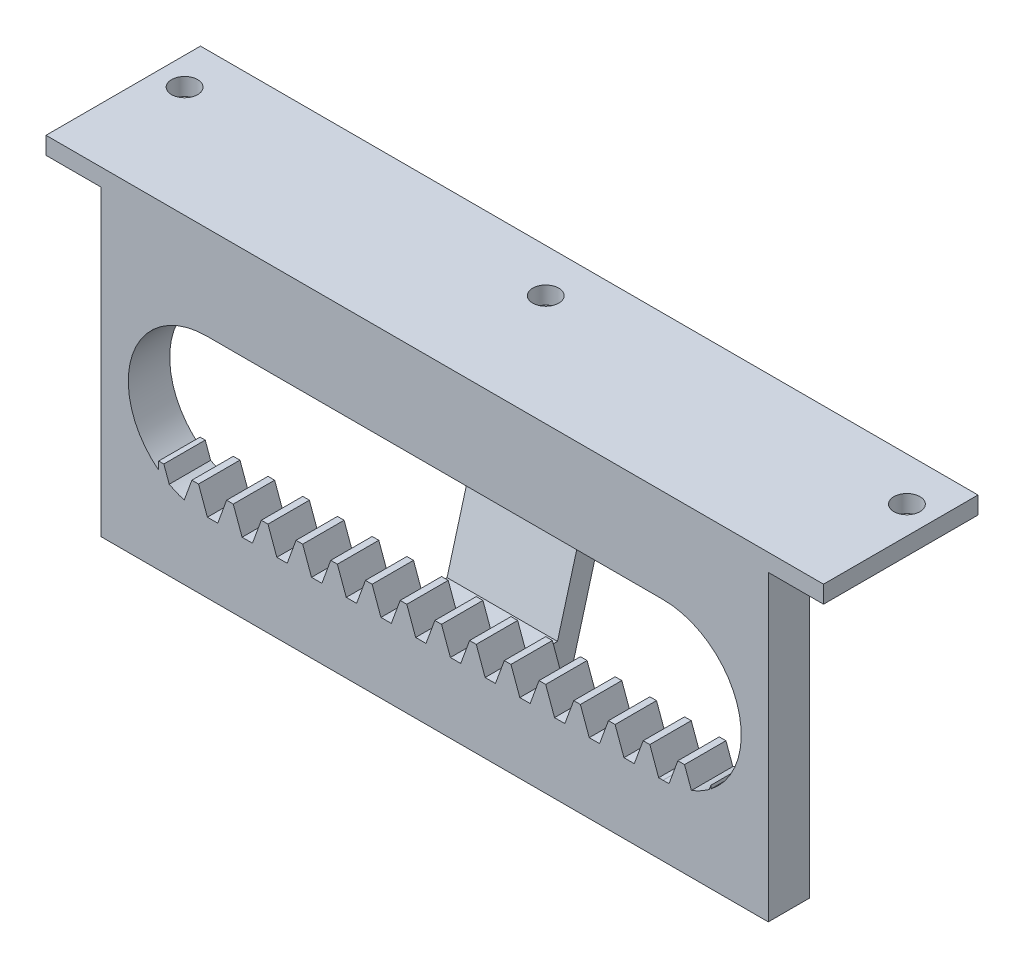
SolidWorks part; units mm, degrees
material "Nylon 101"
ref_plane "Front Plane" through (0, 0, 0) normal (0, 0, 1) x (1, 0, 0)
ref_plane "Top Plane" through (0, 0, 0) normal (0, 1, 0) x (1, 0, 0)
ref_plane "Right Plane" through (0, 0, 0) normal (1, 0, 0) x (0, 0, -1)
sketch "Sketch1" plane through (0, 0, 0) normal (0, 1, 0) x (1, 0, 0)
  line L0 (0, 0) -> (0, 4.7625)
  line L1 (0, 4.7625) -> (63.5, 4.7625)
  line L2 (63.5, 4.7625) -> (63.5, 0)
  line L3 (63.5, 0) -> (0, 0)
  dimension "D1" = 4.7625
  dimension "D2" = 63.5
extrude "Boss-Extrude1" add sketch "Sketch1" along normal blind 4.5
sketch "Sketch2" plane through (0, 0, 0) normal (0, 0, 1) x (1, 0, 0)
  line L0 (0, 3.2275) -> (63.5, 3.2275) construction
  line L1 (0, 4.5) -> (0, 0) construction
  line L2 (63.5, 4.5) -> (63.5, 0) construction
  line L3 (0, 1.7035) -> (63.5, 1.7035) construction
  line L4 (0, 4.5) -> (63.5, 4.5) construction
  line L5 (0, 4.5) -> (0.5952, 4.5) construction
  line L6 (0.5952, 4.5) -> (1.613, 1.7035)
  line L7 (1.613, 1.7035) -> (2.2082, 1.7035)
  line L8 (2.8034, 1.7035) -> (3.8212, 4.5)
  line L9 (3.8212, 4.5) -> (4.4164, 4.5) construction
  line L10 (2.2082, 1.7035) -> (2.8034, 1.7035)
  line L11 (0.5952, 4.5) -> (3.8212, 4.5)
  line L12 (4.5868, 4.5) -> (5.6047, 1.7035)
  line L13 (5.6047, 1.7035) -> (6.1999, 1.7035)
  line L14 (6.795, 1.7035) -> (7.8129, 4.5)
  line L15 (6.1999, 1.7035) -> (6.795, 1.7035)
  line L16 (4.5868, 4.5) -> (7.8129, 4.5)
  line L17 (3.9917, 4.5) -> (4.5868, 4.5) construction
  line L18 (7.8129, 4.5) -> (8.4081, 4.5) construction
  line L19 (8.5785, 4.5) -> (9.5964, 1.7035)
  line L20 (9.5964, 1.7035) -> (10.1915, 1.7035)
  line L21 (10.7867, 1.7035) -> (11.8046, 4.5)
  line L22 (10.1915, 1.7035) -> (10.7867, 1.7035)
  line L23 (8.5785, 4.5) -> (11.8046, 4.5)
  line L24 (7.9834, 4.5) -> (8.5785, 4.5) construction
  line L25 (11.8046, 4.5) -> (12.3997, 4.5) construction
  line L26 (12.5702, 4.5) -> (13.5881, 1.7035)
  line L27 (13.5881, 1.7035) -> (14.1832, 1.7035)
  line L28 (14.7784, 1.7035) -> (15.7962, 4.5)
  line L29 (14.1832, 1.7035) -> (14.7784, 1.7035)
  line L30 (12.5702, 4.5) -> (15.7962, 4.5)
  line L31 (11.975, 4.5) -> (12.5702, 4.5) construction
  line L32 (15.7962, 4.5) -> (16.3914, 4.5) construction
  line L33 (16.5619, 4.5) -> (17.5797, 1.7035)
  line L34 (17.5797, 1.7035) -> (18.1749, 1.7035)
  line L35 (18.7701, 1.7035) -> (19.7879, 4.5)
  line L36 (18.1749, 1.7035) -> (18.7701, 1.7035)
  line L37 (16.5619, 4.5) -> (19.7879, 4.5)
  line L38 (15.9667, 4.5) -> (16.5619, 4.5) construction
  line L39 (19.7879, 4.5) -> (20.3831, 4.5) construction
  line L40 (20.5535, 4.5) -> (21.5714, 1.7035)
  line L41 (21.5714, 1.7035) -> (22.1666, 1.7035)
  line L42 (22.7617, 1.7035) -> (23.7796, 4.5)
  line L43 (22.1666, 1.7035) -> (22.7617, 1.7035)
  line L44 (20.5535, 4.5) -> (23.7796, 4.5)
  line L45 (19.9584, 4.5) -> (20.5535, 4.5) construction
  line L46 (23.7796, 4.5) -> (24.3748, 4.5) construction
  line L47 (24.5452, 4.5) -> (25.5631, 1.7035)
  line L48 (25.5631, 1.7035) -> (26.1582, 1.7035)
  line L49 (26.7534, 1.7035) -> (27.7713, 4.5)
  line L50 (26.1582, 1.7035) -> (26.7534, 1.7035)
  line L51 (24.5452, 4.5) -> (27.7713, 4.5)
  line L52 (23.9501, 4.5) -> (24.5452, 4.5) construction
  line L53 (27.7713, 4.5) -> (28.3664, 4.5) construction
  line L54 (28.5369, 4.5) -> (29.5548, 1.7035)
  line L55 (29.5548, 1.7035) -> (30.1499, 1.7035)
  line L56 (30.7451, 1.7035) -> (31.763, 4.5)
  line L57 (30.1499, 1.7035) -> (30.7451, 1.7035)
  line L58 (28.5369, 4.5) -> (31.763, 4.5)
  line L59 (27.9417, 4.5) -> (28.5369, 4.5) construction
  line L60 (31.763, 4.5) -> (32.3581, 4.5) construction
  line L61 (32.5286, 4.5) -> (33.5464, 1.7035)
  line L62 (33.5464, 1.7035) -> (34.1416, 1.7035)
  line L63 (34.7368, 1.7035) -> (35.7546, 4.5)
  line L64 (34.1416, 1.7035) -> (34.7368, 1.7035)
  line L65 (32.5286, 4.5) -> (35.7546, 4.5)
  line L66 (31.9334, 4.5) -> (32.5286, 4.5) construction
  line L67 (35.7546, 4.5) -> (36.3498, 4.5) construction
  line L68 (36.5203, 4.5) -> (37.5381, 1.7035)
  line L69 (37.5381, 1.7035) -> (38.1333, 1.7035)
  line L70 (38.7284, 1.7035) -> (39.7463, 4.5)
  line L71 (38.1333, 1.7035) -> (38.7284, 1.7035)
  line L72 (36.5203, 4.5) -> (39.7463, 4.5)
  line L73 (35.9251, 4.5) -> (36.5203, 4.5) construction
  line L74 (39.7463, 4.5) -> (40.3415, 4.5) construction
  line L75 (40.5119, 4.5) -> (41.5298, 1.7035)
  line L76 (41.5298, 1.7035) -> (42.125, 1.7035)
  line L77 (42.7201, 1.7035) -> (43.738, 4.5)
  line L78 (42.125, 1.7035) -> (42.7201, 1.7035)
  line L79 (40.5119, 4.5) -> (43.738, 4.5)
  line L80 (39.9168, 4.5) -> (40.5119, 4.5) construction
  line L81 (43.738, 4.5) -> (44.3331, 4.5) construction
  line L82 (44.5036, 4.5) -> (45.5215, 1.7035)
  line L83 (45.5215, 1.7035) -> (46.1166, 1.7035)
  line L84 (46.7118, 1.7035) -> (47.7297, 4.5)
  line L85 (46.1166, 1.7035) -> (46.7118, 1.7035)
  line L86 (44.5036, 4.5) -> (47.7297, 4.5)
  line L87 (43.9084, 4.5) -> (44.5036, 4.5) construction
  line L88 (47.7297, 4.5) -> (48.3248, 4.5) construction
  line L89 (48.4953, 4.5) -> (49.5131, 1.7035)
  line L90 (49.5131, 1.7035) -> (50.1083, 1.7035)
  line L91 (50.7035, 1.7035) -> (51.7213, 4.5)
  line L92 (50.1083, 1.7035) -> (50.7035, 1.7035)
  line L93 (48.4953, 4.5) -> (51.7213, 4.5)
  line L94 (47.9001, 4.5) -> (48.4953, 4.5) construction
  line L95 (51.7213, 4.5) -> (52.3165, 4.5) construction
  line L96 (52.487, 4.5) -> (53.5048, 1.7035)
  line L97 (53.5048, 1.7035) -> (54.1, 1.7035)
  line L98 (54.6952, 1.7035) -> (55.713, 4.5)
  line L99 (54.1, 1.7035) -> (54.6952, 1.7035)
  line L100 (52.487, 4.5) -> (55.713, 4.5)
  line L101 (51.8918, 4.5) -> (52.487, 4.5) construction
  line L102 (55.713, 4.5) -> (56.3082, 4.5) construction
  line L103 (56.4786, 4.5) -> (57.4965, 1.7035)
  line L104 (57.4965, 1.7035) -> (58.0917, 1.7035)
  line L105 (58.6868, 1.7035) -> (59.7047, 4.5)
  line L106 (58.0917, 1.7035) -> (58.6868, 1.7035)
  line L107 (56.4786, 4.5) -> (59.7047, 4.5)
  line L108 (55.8835, 4.5) -> (56.4786, 4.5) construction
  line L109 (59.7047, 4.5) -> (60.2999, 4.5) construction
  line L110 (60.4703, 4.5) -> (61.4882, 1.7035)
  line L111 (61.4882, 1.7035) -> (62.0833, 1.7035)
  line L112 (62.6785, 1.7035) -> (63.6964, 4.5)
  line L113 (62.0833, 1.7035) -> (62.6785, 1.7035)
  line L114 (60.4703, 4.5) -> (63.6964, 4.5)
  line L115 (59.8751, 4.5) -> (60.4703, 4.5) construction
  line L116 (63.6964, 4.5) -> (64.2915, 4.5) construction
  line L117 (64.462, 4.5) -> (65.4798, 1.7035)
  line L118 (65.4798, 1.7035) -> (66.075, 1.7035)
  line L119 (66.6702, 1.7035) -> (67.688, 4.5)
  line L120 (66.075, 1.7035) -> (66.6702, 1.7035)
  line L121 (64.462, 4.5) -> (67.688, 4.5)
  line L122 (63.8668, 4.5) -> (64.462, 4.5) construction
  line L123 (67.688, 4.5) -> (68.2832, 4.5) construction
  line L124 (68.4537, 4.5) -> (69.4715, 1.7035)
  line L125 (69.4715, 1.7035) -> (70.0667, 1.7035)
  line L126 (70.6619, 1.7035) -> (71.6797, 4.5)
  line L127 (70.0667, 1.7035) -> (70.6619, 1.7035)
  line L128 (68.4537, 4.5) -> (71.6797, 4.5)
  line L129 (67.8585, 4.5) -> (68.4537, 4.5) construction
  line L130 (71.6797, 4.5) -> (72.2749, 4.5) construction
  line L131 (72.4453, 4.5) -> (73.4632, 1.7035)
  line L132 (73.4632, 1.7035) -> (74.0584, 1.7035)
  line L133 (74.6535, 1.7035) -> (75.6714, 4.5)
  line L134 (74.0584, 1.7035) -> (74.6535, 1.7035)
  line L135 (72.4453, 4.5) -> (75.6714, 4.5)
  line L136 (71.8502, 4.5) -> (72.4453, 4.5) construction
  line L137 (75.6714, 4.5) -> (76.2666, 4.5) construction
  line L138 (76.437, 4.5) -> (77.4549, 1.7035)
  line L139 (77.4549, 1.7035) -> (78.05, 1.7035)
  line L140 (78.6452, 1.7035) -> (79.6631, 4.5)
  line L141 (78.05, 1.7035) -> (78.6452, 1.7035)
  line L142 (76.437, 4.5) -> (79.6631, 4.5)
  line L143 (75.8418, 4.5) -> (76.437, 4.5) construction
  line L144 (79.6631, 4.5) -> (80.2582, 4.5) construction
  line L145 (80.4287, 4.5) -> (81.4465, 1.7035)
  line L146 (81.4465, 1.7035) -> (82.0417, 1.7035)
  line L147 (82.6369, 1.7035) -> (83.6547, 4.5)
  line L148 (82.0417, 1.7035) -> (82.6369, 1.7035)
  line L149 (80.4287, 4.5) -> (83.6547, 4.5)
  line L150 (79.8335, 4.5) -> (80.4287, 4.5) construction
  line L151 (83.6547, 4.5) -> (84.2499, 4.5) construction
  line L152 (84.4204, 4.5) -> (85.4382, 1.7035)
  line L153 (85.4382, 1.7035) -> (86.0334, 1.7035)
  line L154 (86.6286, 1.7035) -> (87.6464, 4.5)
  line L155 (86.0334, 1.7035) -> (86.6286, 1.7035)
  line L156 (84.4204, 4.5) -> (87.6464, 4.5)
  line L157 (83.8252, 4.5) -> (84.4204, 4.5) construction
  line L158 (87.6464, 4.5) -> (88.2416, 4.5) construction
  line L159 (88.412, 4.5) -> (89.4299, 1.7035)
  line L160 (89.4299, 1.7035) -> (90.0251, 1.7035)
  line L161 (90.6202, 1.7035) -> (91.6381, 4.5)
  line L162 (90.0251, 1.7035) -> (90.6202, 1.7035)
  line L163 (88.412, 4.5) -> (91.6381, 4.5)
  line L164 (87.8169, 4.5) -> (88.412, 4.5) construction
  line L165 (91.6381, 4.5) -> (92.2333, 4.5) construction
  line L166 (92.4037, 4.5) -> (93.4216, 1.7035)
  line L167 (93.4216, 1.7035) -> (94.0167, 1.7035)
  line L168 (94.6119, 1.7035) -> (95.6298, 4.5)
  line L169 (94.0167, 1.7035) -> (94.6119, 1.7035)
  line L170 (92.4037, 4.5) -> (95.6298, 4.5)
  line L171 (91.8086, 4.5) -> (92.4037, 4.5) construction
  line L172 (95.6298, 4.5) -> (96.2249, 4.5) construction
  line L173 (96.3954, 4.5) -> (97.4133, 1.7035)
  line L174 (97.4133, 1.7035) -> (98.0084, 1.7035)
  line L175 (98.6036, 1.7035) -> (99.6214, 4.5)
  line L176 (98.0084, 1.7035) -> (98.6036, 1.7035)
  line L177 (96.3954, 4.5) -> (99.6214, 4.5)
  line L178 (95.8002, 4.5) -> (96.3954, 4.5) construction
  line L179 (99.6214, 4.5) -> (100.2166, 4.5) construction
  line L180 (100.3871, 4.5) -> (101.4049, 1.7035)
  line L181 (101.4049, 1.7035) -> (102.0001, 1.7035)
  line L182 (102.5953, 1.7035) -> (103.6131, 4.5)
  line L183 (102.0001, 1.7035) -> (102.5953, 1.7035)
  line L184 (100.3871, 4.5) -> (103.6131, 4.5)
  line L185 (99.7919, 4.5) -> (100.3871, 4.5) construction
  line L186 (103.6131, 4.5) -> (104.2083, 4.5) construction
  line L187 (104.3787, 4.5) -> (105.3966, 1.7035)
  line L188 (105.3966, 1.7035) -> (105.9918, 1.7035)
  line L189 (106.5869, 1.7035) -> (107.6048, 4.5)
  line L190 (105.9918, 1.7035) -> (106.5869, 1.7035)
  line L191 (104.3787, 4.5) -> (107.6048, 4.5)
  line L192 (103.7836, 4.5) -> (104.3787, 4.5) construction
  line L193 (107.6048, 4.5) -> (108.2, 4.5) construction
  line L194 (108.3704, 4.5) -> (109.3883, 1.7035)
  line L195 (109.3883, 1.7035) -> (109.9835, 1.7035)
  line L196 (110.5786, 1.7035) -> (111.5965, 4.5)
  line L197 (109.9835, 1.7035) -> (110.5786, 1.7035)
  line L198 (108.3704, 4.5) -> (111.5965, 4.5)
  line L199 (107.7753, 4.5) -> (108.3704, 4.5) construction
  line L200 (111.5965, 4.5) -> (112.1916, 4.5) construction
  line L201 (112.3621, 4.5) -> (113.38, 1.7035)
  line L202 (113.38, 1.7035) -> (113.9751, 1.7035)
  line L203 (114.5703, 1.7035) -> (115.5882, 4.5)
  line L204 (113.9751, 1.7035) -> (114.5703, 1.7035)
  line L205 (112.3621, 4.5) -> (115.5882, 4.5)
  line L206 (111.7669, 4.5) -> (112.3621, 4.5) construction
  line L207 (115.5882, 4.5) -> (116.1833, 4.5) construction
  line L208 (116.3538, 4.5) -> (117.3716, 1.7035)
  line L209 (117.3716, 1.7035) -> (117.9668, 1.7035)
  line L210 (118.562, 1.7035) -> (119.5798, 4.5)
  line L211 (117.9668, 1.7035) -> (118.562, 1.7035)
  line L212 (116.3538, 4.5) -> (119.5798, 4.5)
  line L213 (115.7586, 4.5) -> (116.3538, 4.5) construction
  line L214 (119.5798, 4.5) -> (120.175, 4.5) construction
  line L215 (120.3455, 4.5) -> (121.3633, 1.7035)
  line L216 (121.3633, 1.7035) -> (121.9585, 1.7035)
  line L217 (122.5536, 1.7035) -> (123.5715, 4.5)
  line L218 (121.9585, 1.7035) -> (122.5536, 1.7035)
  line L219 (120.3455, 4.5) -> (123.5715, 4.5)
  line L220 (119.7503, 4.5) -> (120.3455, 4.5) construction
  line L221 (123.5715, 4.5) -> (124.1667, 4.5) construction
  line L222 (124.3371, 4.5) -> (125.355, 1.7035)
  line L223 (125.355, 1.7035) -> (125.9502, 1.7035)
  line L224 (126.5453, 1.7035) -> (127.5632, 4.5)
  line L225 (125.9502, 1.7035) -> (126.5453, 1.7035)
  line L226 (124.3371, 4.5) -> (127.5632, 4.5)
  line L227 (123.742, 4.5) -> (124.3371, 4.5) construction
  line L228 (127.5632, 4.5) -> (128.1583, 4.5) construction
  line L229 (128.3288, 4.5) -> (129.3467, 1.7035)
  line L230 (129.3467, 1.7035) -> (129.9418, 1.7035)
  line L231 (130.537, 1.7035) -> (131.5549, 4.5)
  line L232 (129.9418, 1.7035) -> (130.537, 1.7035)
  line L233 (128.3288, 4.5) -> (131.5549, 4.5)
  line L234 (127.7336, 4.5) -> (128.3288, 4.5) construction
  line L235 (131.5549, 4.5) -> (132.15, 4.5) construction
  line L236 (132.3205, 4.5) -> (133.3383, 1.7035)
  line L237 (133.3383, 1.7035) -> (133.9335, 1.7035)
  line L238 (134.5287, 1.7035) -> (135.5465, 4.5)
  line L239 (133.9335, 1.7035) -> (134.5287, 1.7035)
  line L240 (132.3205, 4.5) -> (135.5465, 4.5)
  line L241 (131.7253, 4.5) -> (132.3205, 4.5) construction
  line L242 (135.5465, 4.5) -> (136.1417, 4.5) construction
  line L243 (136.3122, 4.5) -> (137.33, 1.7035)
  line L244 (137.33, 1.7035) -> (137.9252, 1.7035)
  line L245 (138.5204, 1.7035) -> (139.5382, 4.5)
  line L246 (137.9252, 1.7035) -> (138.5204, 1.7035)
  line L247 (136.3122, 4.5) -> (139.5382, 4.5)
  line L248 (135.717, 4.5) -> (136.3122, 4.5) construction
  line L249 (139.5382, 4.5) -> (140.1334, 4.5) construction
  line L250 (140.3038, 4.5) -> (141.3217, 1.7035)
  line L251 (141.3217, 1.7035) -> (141.9169, 1.7035)
  line L252 (142.512, 1.7035) -> (143.5299, 4.5)
  line L253 (141.9169, 1.7035) -> (142.512, 1.7035)
  line L254 (140.3038, 4.5) -> (143.5299, 4.5)
  line L255 (139.7087, 4.5) -> (140.3038, 4.5) construction
  line L256 (143.5299, 4.5) -> (144.1251, 4.5) construction
  line L257 (144.2955, 4.5) -> (145.3134, 1.7035)
  line L258 (145.3134, 1.7035) -> (145.9085, 1.7035)
  line L259 (146.5037, 1.7035) -> (147.5216, 4.5)
  line L260 (145.9085, 1.7035) -> (146.5037, 1.7035)
  line L261 (144.2955, 4.5) -> (147.5216, 4.5)
  line L262 (143.7003, 4.5) -> (144.2955, 4.5) construction
  line L263 (147.5216, 4.5) -> (148.1167, 4.5) construction
  line L264 (148.2872, 4.5) -> (149.305, 1.7035)
  line L265 (149.305, 1.7035) -> (149.9002, 1.7035)
  line L266 (150.4954, 1.7035) -> (151.5132, 4.5)
  line L267 (149.9002, 1.7035) -> (150.4954, 1.7035)
  line L268 (148.2872, 4.5) -> (151.5132, 4.5)
  line L269 (147.692, 4.5) -> (148.2872, 4.5) construction
  line L270 (151.5132, 4.5) -> (152.1084, 4.5) construction
  line L271 (152.2789, 4.5) -> (153.2967, 1.7035)
  line L272 (153.2967, 1.7035) -> (153.8919, 1.7035)
  line L273 (154.4871, 1.7035) -> (155.5049, 4.5)
  line L274 (153.8919, 1.7035) -> (154.4871, 1.7035)
  line L275 (152.2789, 4.5) -> (155.5049, 4.5)
  line L276 (151.6837, 4.5) -> (152.2789, 4.5) construction
  line L277 (155.5049, 4.5) -> (156.1001, 4.5) construction
  line L278 (156.2705, 4.5) -> (157.2884, 1.7035)
  line L279 (157.2884, 1.7035) -> (157.8836, 1.7035)
  line L280 (158.4787, 1.7035) -> (159.4966, 4.5)
  line L281 (157.8836, 1.7035) -> (158.4787, 1.7035)
  line L282 (156.2705, 4.5) -> (159.4966, 4.5)
  line L283 (155.6754, 4.5) -> (156.2705, 4.5) construction
  line L284 (159.4966, 4.5) -> (160.0918, 4.5) construction
  line L285 (160.2622, 4.5) -> (161.2801, 1.7035)
  line L286 (161.2801, 1.7035) -> (161.8752, 1.7035)
  line L287 (162.4704, 1.7035) -> (163.4883, 4.5)
  line L288 (161.8752, 1.7035) -> (162.4704, 1.7035)
  line L289 (160.2622, 4.5) -> (163.4883, 4.5)
  line L290 (159.667, 4.5) -> (160.2622, 4.5) construction
  line L291 (163.4883, 4.5) -> (164.0834, 4.5) construction
  line L292 (164.2539, 4.5) -> (165.2718, 1.7035)
  line L293 (165.2718, 1.7035) -> (165.8669, 1.7035)
  line L294 (166.4621, 1.7035) -> (167.4799, 4.5)
  line L295 (165.8669, 1.7035) -> (166.4621, 1.7035)
  line L296 (164.2539, 4.5) -> (167.4799, 4.5)
  line L297 (163.6587, 4.5) -> (164.2539, 4.5) construction
  line L298 (167.4799, 4.5) -> (168.0751, 4.5) construction
  line L299 (168.2456, 4.5) -> (169.2634, 1.7035)
  line L300 (169.2634, 1.7035) -> (169.8586, 1.7035)
  line L301 (170.4538, 1.7035) -> (171.4716, 4.5)
  line L302 (169.8586, 1.7035) -> (170.4538, 1.7035)
  line L303 (168.2456, 4.5) -> (171.4716, 4.5)
  line L304 (167.6504, 4.5) -> (168.2456, 4.5) construction
  line L305 (171.4716, 4.5) -> (172.0668, 4.5) construction
  line L306 (172.2372, 4.5) -> (173.2551, 1.7035)
  line L307 (173.2551, 1.7035) -> (173.8503, 1.7035)
  line L308 (174.4454, 1.7035) -> (175.4633, 4.5)
  line L309 (173.8503, 1.7035) -> (174.4454, 1.7035)
  line L310 (172.2372, 4.5) -> (175.4633, 4.5)
  line L311 (171.6421, 4.5) -> (172.2372, 4.5) construction
  line L312 (175.4633, 4.5) -> (176.0585, 4.5) construction
  line L313 (176.2289, 4.5) -> (177.2468, 1.7035)
  line L314 (177.2468, 1.7035) -> (177.8419, 1.7035)
  line L315 (178.4371, 1.7035) -> (179.455, 4.5)
  line L316 (177.8419, 1.7035) -> (178.4371, 1.7035)
  line L317 (176.2289, 4.5) -> (179.455, 4.5)
  line L318 (175.6338, 4.5) -> (176.2289, 4.5) construction
  line L319 (179.455, 4.5) -> (180.0501, 4.5) construction
  line L320 (180.2206, 4.5) -> (181.2385, 1.7035)
  line L321 (181.2385, 1.7035) -> (181.8336, 1.7035)
  line L322 (182.4288, 1.7035) -> (183.4466, 4.5)
  line L323 (181.8336, 1.7035) -> (182.4288, 1.7035)
  line L324 (180.2206, 4.5) -> (183.4466, 4.5)
  line L325 (179.6254, 4.5) -> (180.2206, 4.5) construction
  line L326 (183.4466, 4.5) -> (184.0418, 4.5) construction
  line L327 (184.2123, 4.5) -> (185.2301, 1.7035)
  line L328 (185.2301, 1.7035) -> (185.8253, 1.7035)
  line L329 (186.4205, 1.7035) -> (187.4383, 4.5)
  line L330 (185.8253, 1.7035) -> (186.4205, 1.7035)
  line L331 (184.2123, 4.5) -> (187.4383, 4.5)
  line L332 (183.6171, 4.5) -> (184.2123, 4.5) construction
  line L333 (187.4383, 4.5) -> (188.0335, 4.5) construction
  line L334 (188.204, 4.5) -> (189.2218, 1.7035)
  line L335 (189.2218, 1.7035) -> (189.817, 1.7035)
  line L336 (190.4121, 1.7035) -> (191.43, 4.5)
  line L337 (189.817, 1.7035) -> (190.4121, 1.7035)
  line L338 (188.204, 4.5) -> (191.43, 4.5)
  line L339 (187.6088, 4.5) -> (188.204, 4.5) construction
  line L340 (191.43, 4.5) -> (192.0252, 4.5) construction
  line L341 (192.1956, 4.5) -> (193.2135, 1.7035)
  line L342 (193.2135, 1.7035) -> (193.8087, 1.7035)
  line L343 (194.4038, 1.7035) -> (195.4217, 4.5)
  line L344 (193.8087, 1.7035) -> (194.4038, 1.7035)
  line L345 (192.1956, 4.5) -> (195.4217, 4.5)
  line L346 (191.6005, 4.5) -> (192.1956, 4.5) construction
  line L347 (195.4217, 4.5) -> (196.0168, 4.5) construction
  line L348 (196.1873, 4.5) -> (197.2052, 1.7035)
  line L349 (197.2052, 1.7035) -> (197.8003, 1.7035)
  line L350 (198.3955, 1.7035) -> (199.4134, 4.5)
  line L351 (197.8003, 1.7035) -> (198.3955, 1.7035)
  line L352 (196.1873, 4.5) -> (199.4134, 4.5)
  line L353 (195.5921, 4.5) -> (196.1873, 4.5) construction
  line L354 (199.4134, 4.5) -> (200.0085, 4.5) construction
  line L355 (200.179, 4.5) -> (201.1968, 1.7035)
  line L356 (201.1968, 1.7035) -> (201.792, 1.7035)
  line L357 (202.3872, 1.7035) -> (203.405, 4.5)
  line L358 (201.792, 1.7035) -> (202.3872, 1.7035)
  line L359 (200.179, 4.5) -> (203.405, 4.5)
  line L360 (199.5838, 4.5) -> (200.179, 4.5) construction
  line L361 (203.405, 4.5) -> (204.0002, 4.5) construction
  line L362 (204.1707, 4.5) -> (205.1885, 1.7035)
  line L363 (205.1885, 1.7035) -> (205.7837, 1.7035)
  line L364 (206.3788, 1.7035) -> (207.3967, 4.5)
  line L365 (205.7837, 1.7035) -> (206.3788, 1.7035)
  line L366 (204.1707, 4.5) -> (207.3967, 4.5)
  line L367 (203.5755, 4.5) -> (204.1707, 4.5) construction
  line L368 (207.3967, 4.5) -> (207.9919, 4.5) construction
  line L369 (208.1623, 4.5) -> (209.1802, 1.7035)
  line L370 (209.1802, 1.7035) -> (209.7754, 1.7035)
  line L371 (210.3705, 1.7035) -> (211.3884, 4.5)
  line L372 (209.7754, 1.7035) -> (210.3705, 1.7035)
  line L373 (208.1623, 4.5) -> (211.3884, 4.5)
  line L374 (207.5672, 4.5) -> (208.1623, 4.5) construction
  line L375 (211.3884, 4.5) -> (211.9835, 4.5) construction
  line L376 (212.154, 4.5) -> (213.1719, 1.7035)
  line L377 (213.1719, 1.7035) -> (213.767, 1.7035)
  line L378 (214.3622, 1.7035) -> (215.3801, 4.5)
  line L379 (213.767, 1.7035) -> (214.3622, 1.7035)
  line L380 (212.154, 4.5) -> (215.3801, 4.5)
  line L381 (211.5588, 4.5) -> (212.154, 4.5) construction
  line L382 (215.3801, 4.5) -> (215.9752, 4.5) construction
  line L383 (216.1457, 4.5) -> (217.1635, 1.7035)
  line L384 (217.1635, 1.7035) -> (217.7587, 1.7035)
  line L385 (218.3539, 1.7035) -> (219.3717, 4.5)
  line L386 (217.7587, 1.7035) -> (218.3539, 1.7035)
  line L387 (216.1457, 4.5) -> (219.3717, 4.5)
  line L388 (215.5505, 4.5) -> (216.1457, 4.5) construction
  line L389 (219.3717, 4.5) -> (219.9669, 4.5) construction
  line L390 (220.1374, 4.5) -> (221.1552, 1.7035)
  line L391 (221.1552, 1.7035) -> (221.7504, 1.7035)
  line L392 (222.3456, 1.7035) -> (223.3634, 4.5)
  line L393 (221.7504, 1.7035) -> (222.3456, 1.7035)
  line L394 (220.1374, 4.5) -> (223.3634, 4.5)
  line L395 (219.5422, 4.5) -> (220.1374, 4.5) construction
  line L396 (223.3634, 4.5) -> (223.9586, 4.5) construction
  line L397 (224.129, 4.5) -> (225.1469, 1.7035)
  line L398 (225.1469, 1.7035) -> (225.7421, 1.7035)
  line L399 (226.3372, 1.7035) -> (227.3551, 4.5)
  line L400 (225.7421, 1.7035) -> (226.3372, 1.7035)
  line L401 (224.129, 4.5) -> (227.3551, 4.5)
  line L402 (223.5339, 4.5) -> (224.129, 4.5) construction
  line L403 (227.3551, 4.5) -> (227.9503, 4.5) construction
  line L404 (228.1207, 4.5) -> (229.1386, 1.7035)
  line L405 (229.1386, 1.7035) -> (229.7337, 1.7035)
  line L406 (230.3289, 1.7035) -> (231.3468, 4.5)
  line L407 (229.7337, 1.7035) -> (230.3289, 1.7035)
  line L408 (228.1207, 4.5) -> (231.3468, 4.5)
  line L409 (227.5255, 4.5) -> (228.1207, 4.5) construction
  line L410 (231.3468, 4.5) -> (231.9419, 4.5) construction
  line L411 (232.1124, 4.5) -> (233.1302, 1.7035)
  line L412 (233.1302, 1.7035) -> (233.7254, 1.7035)
  line L413 (234.3206, 1.7035) -> (235.3384, 4.5)
  line L414 (233.7254, 1.7035) -> (234.3206, 1.7035)
  line L415 (232.1124, 4.5) -> (235.3384, 4.5)
  line L416 (231.5172, 4.5) -> (232.1124, 4.5) construction
  line L417 (235.3384, 4.5) -> (235.9336, 4.5) construction
  line L418 (236.1041, 4.5) -> (237.1219, 1.7035)
  line L419 (237.1219, 1.7035) -> (237.7171, 1.7035)
  line L420 (238.3123, 1.7035) -> (239.3301, 4.5)
  line L421 (237.7171, 1.7035) -> (238.3123, 1.7035)
  line L422 (236.1041, 4.5) -> (239.3301, 4.5)
  line L423 (235.5089, 4.5) -> (236.1041, 4.5) construction
  line L424 (239.3301, 4.5) -> (239.9253, 4.5) construction
  line L425 (240.0957, 4.5) -> (241.1136, 1.7035)
  line L426 (241.1136, 1.7035) -> (241.7088, 1.7035)
  line L427 (242.3039, 1.7035) -> (243.3218, 4.5)
  line L428 (241.7088, 1.7035) -> (242.3039, 1.7035)
  line L429 (240.0957, 4.5) -> (243.3218, 4.5)
  line L430 (239.5006, 4.5) -> (240.0957, 4.5) construction
  line L431 (243.3218, 4.5) -> (243.917, 4.5) construction
  line L432 (244.0874, 4.5) -> (245.1053, 1.7035)
  line L433 (245.1053, 1.7035) -> (245.7004, 1.7035)
  line L434 (246.2956, 1.7035) -> (247.3135, 4.5)
  line L435 (245.7004, 1.7035) -> (246.2956, 1.7035)
  line L436 (244.0874, 4.5) -> (247.3135, 4.5)
  line L437 (243.4923, 4.5) -> (244.0874, 4.5) construction
  line L438 (247.3135, 4.5) -> (247.9086, 4.5) construction
  line L439 (248.0791, 4.5) -> (249.097, 1.7035)
  line L440 (249.097, 1.7035) -> (249.6921, 1.7035)
  line L441 (250.2873, 1.7035) -> (251.3051, 4.5)
  line L442 (249.6921, 1.7035) -> (250.2873, 1.7035)
  line L443 (248.0791, 4.5) -> (251.3051, 4.5)
  line L444 (247.4839, 4.5) -> (248.0791, 4.5) construction
  line L445 (251.3051, 4.5) -> (251.9003, 4.5) construction
  line L446 (252.0708, 4.5) -> (253.0886, 1.7035)
  line L447 (253.0886, 1.7035) -> (253.6838, 1.7035)
  line L448 (254.279, 1.7035) -> (255.2968, 4.5)
  line L449 (253.6838, 1.7035) -> (254.279, 1.7035)
  line L450 (252.0708, 4.5) -> (255.2968, 4.5)
  line L451 (251.4756, 4.5) -> (252.0708, 4.5) construction
  line L452 (255.2968, 4.5) -> (255.892, 4.5) construction
  line L453 (256.0624, 4.5) -> (257.0803, 1.7035)
  line L454 (257.0803, 1.7035) -> (257.6755, 1.7035)
  line L455 (258.2706, 1.7035) -> (259.2885, 4.5)
  line L456 (257.6755, 1.7035) -> (258.2706, 1.7035)
  line L457 (256.0624, 4.5) -> (259.2885, 4.5)
  line L458 (255.4673, 4.5) -> (256.0624, 4.5) construction
  line L459 (259.2885, 4.5) -> (259.8837, 4.5) construction
  line L460 (260.0541, 4.5) -> (261.072, 1.7035)
  line L461 (261.072, 1.7035) -> (261.6671, 1.7035)
  line L462 (262.2623, 1.7035) -> (263.2802, 4.5)
  line L463 (261.6671, 1.7035) -> (262.2623, 1.7035)
  line L464 (260.0541, 4.5) -> (263.2802, 4.5)
  line L465 (259.459, 4.5) -> (260.0541, 4.5) construction
  line L466 (263.2802, 4.5) -> (263.8753, 4.5) construction
  line L467 (264.0458, 4.5) -> (265.0637, 1.7035)
  line L468 (265.0637, 1.7035) -> (265.6588, 1.7035)
  line L469 (266.254, 1.7035) -> (267.2718, 4.5)
  line L470 (265.6588, 1.7035) -> (266.254, 1.7035)
  line L471 (264.0458, 4.5) -> (267.2718, 4.5)
  line L472 (263.4506, 4.5) -> (264.0458, 4.5) construction
  line L473 (267.2718, 4.5) -> (267.867, 4.5) construction
  line L474 (268.0375, 4.5) -> (269.0553, 1.7035)
  line L475 (269.0553, 1.7035) -> (269.6505, 1.7035)
  line L476 (270.2457, 1.7035) -> (271.2635, 4.5)
  line L477 (269.6505, 1.7035) -> (270.2457, 1.7035)
  line L478 (268.0375, 4.5) -> (271.2635, 4.5)
  line L479 (267.4423, 4.5) -> (268.0375, 4.5) construction
  line L480 (271.2635, 4.5) -> (271.8587, 4.5) construction
  line L481 (272.0292, 4.5) -> (273.047, 1.7035)
  line L482 (273.047, 1.7035) -> (273.6422, 1.7035)
  line L483 (274.2373, 1.7035) -> (275.2552, 4.5)
  line L484 (273.6422, 1.7035) -> (274.2373, 1.7035)
  line L485 (272.0292, 4.5) -> (275.2552, 4.5)
  line L486 (271.434, 4.5) -> (272.0292, 4.5) construction
  line L487 (275.2552, 4.5) -> (275.8504, 4.5) construction
  line L488 (276.0208, 4.5) -> (277.0387, 1.7035)
  line L489 (277.0387, 1.7035) -> (277.6339, 1.7035)
  line L490 (278.229, 1.7035) -> (279.2469, 4.5)
  line L491 (277.6339, 1.7035) -> (278.229, 1.7035)
  line L492 (276.0208, 4.5) -> (279.2469, 4.5)
  line L493 (275.4257, 4.5) -> (276.0208, 4.5) construction
  line L494 (279.2469, 4.5) -> (279.842, 4.5) construction
  line L495 (280.0125, 4.5) -> (281.0304, 1.7035)
  line L496 (281.0304, 1.7035) -> (281.6255, 1.7035)
  line L497 (282.2207, 1.7035) -> (283.2386, 4.5)
  line L498 (281.6255, 1.7035) -> (282.2207, 1.7035)
  line L499 (280.0125, 4.5) -> (283.2386, 4.5)
  line L500 (279.4173, 4.5) -> (280.0125, 4.5) construction
  line L501 (283.2386, 4.5) -> (283.8337, 4.5) construction
  line L502 (284.0042, 4.5) -> (285.022, 1.7035)
  line L503 (285.022, 1.7035) -> (285.6172, 1.7035)
  line L504 (286.2124, 1.7035) -> (287.2302, 4.5)
  line L505 (285.6172, 1.7035) -> (286.2124, 1.7035)
  line L506 (284.0042, 4.5) -> (287.2302, 4.5)
  line L507 (283.409, 4.5) -> (284.0042, 4.5) construction
  line L508 (287.2302, 4.5) -> (287.8254, 4.5) construction
  line L509 (287.9959, 4.5) -> (289.0137, 1.7035)
  line L510 (289.0137, 1.7035) -> (289.6089, 1.7035)
  line L511 (290.204, 1.7035) -> (291.2219, 4.5)
  line L512 (289.6089, 1.7035) -> (290.204, 1.7035)
  line L513 (287.9959, 4.5) -> (291.2219, 4.5)
  line L514 (287.4007, 4.5) -> (287.9959, 4.5) construction
  line L515 (291.2219, 4.5) -> (291.8171, 4.5) construction
  line L516 (291.9875, 4.5) -> (293.0054, 1.7035)
  line L517 (293.0054, 1.7035) -> (293.6006, 1.7035)
  line L518 (294.1957, 1.7035) -> (295.2136, 4.5)
  line L519 (293.6006, 1.7035) -> (294.1957, 1.7035)
  line L520 (291.9875, 4.5) -> (295.2136, 4.5)
  line L521 (291.3924, 4.5) -> (291.9875, 4.5) construction
  line L522 (295.2136, 4.5) -> (295.8087, 4.5) construction
  line L523 (295.9792, 4.5) -> (296.9971, 1.7035)
  line L524 (296.9971, 1.7035) -> (297.5922, 1.7035)
  line L525 (298.1874, 1.7035) -> (299.2053, 4.5)
  line L526 (297.5922, 1.7035) -> (298.1874, 1.7035)
  line L527 (295.9792, 4.5) -> (299.2053, 4.5)
  line L528 (295.384, 4.5) -> (295.9792, 4.5) construction
  line L529 (299.2053, 4.5) -> (299.8004, 4.5) construction
  line L530 (299.9709, 4.5) -> (300.9887, 1.7035)
  line L531 (300.9887, 1.7035) -> (301.5839, 1.7035)
  line L532 (302.1791, 1.7035) -> (303.1969, 4.5)
  line L533 (301.5839, 1.7035) -> (302.1791, 1.7035)
  line L534 (299.9709, 4.5) -> (303.1969, 4.5)
  line L535 (299.3757, 4.5) -> (299.9709, 4.5) construction
  line L536 (303.1969, 4.5) -> (303.7921, 4.5) construction
  line L537 (303.9626, 4.5) -> (304.9804, 1.7035)
  line L538 (304.9804, 1.7035) -> (305.5756, 1.7035)
  line L539 (306.1708, 1.7035) -> (307.1886, 4.5)
  line L540 (305.5756, 1.7035) -> (306.1708, 1.7035)
  line L541 (303.9626, 4.5) -> (307.1886, 4.5)
  line L542 (303.3674, 4.5) -> (303.9626, 4.5) construction
  line L543 (307.1886, 4.5) -> (307.7838, 4.5) construction
  line L544 (307.9542, 4.5) -> (308.9721, 1.7035)
  line L545 (308.9721, 1.7035) -> (309.5673, 1.7035)
  line L546 (310.1624, 1.7035) -> (311.1803, 4.5)
  line L547 (309.5673, 1.7035) -> (310.1624, 1.7035)
  line L548 (307.9542, 4.5) -> (311.1803, 4.5)
  line L549 (307.3591, 4.5) -> (307.9542, 4.5) construction
  line L550 (311.1803, 4.5) -> (311.7755, 4.5) construction
  line L551 (311.9459, 4.5) -> (312.9638, 1.7035)
  line L552 (312.9638, 1.7035) -> (313.5589, 1.7035)
  line L553 (314.1541, 1.7035) -> (315.172, 4.5)
  line L554 (313.5589, 1.7035) -> (314.1541, 1.7035)
  line L555 (311.9459, 4.5) -> (315.172, 4.5)
  line L556 (311.3507, 4.5) -> (311.9459, 4.5) construction
  line L557 (315.172, 4.5) -> (315.7671, 4.5) construction
  line L558 (315.9376, 4.5) -> (316.9554, 1.7035)
  line L559 (316.9554, 1.7035) -> (317.5506, 1.7035)
  line L560 (318.1458, 1.7035) -> (319.1636, 4.5)
  line L561 (317.5506, 1.7035) -> (318.1458, 1.7035)
  line L562 (315.9376, 4.5) -> (319.1636, 4.5)
  line L563 (315.3424, 4.5) -> (315.9376, 4.5) construction
  line L564 (319.1636, 4.5) -> (319.7588, 4.5) construction
  line L565 (319.9293, 4.5) -> (320.9471, 1.7035)
  line L566 (320.9471, 1.7035) -> (321.5423, 1.7035)
  line L567 (322.1375, 1.7035) -> (323.1553, 4.5)
  line L568 (321.5423, 1.7035) -> (322.1375, 1.7035)
  line L569 (319.9293, 4.5) -> (323.1553, 4.5)
  line L570 (319.3341, 4.5) -> (319.9293, 4.5) construction
  line L571 (323.1553, 4.5) -> (323.7505, 4.5) construction
  line L572 (323.9209, 4.5) -> (324.9388, 1.7035)
  line L573 (324.9388, 1.7035) -> (325.534, 1.7035)
  line L574 (326.1291, 1.7035) -> (327.147, 4.5)
  line L575 (325.534, 1.7035) -> (326.1291, 1.7035)
  line L576 (323.9209, 4.5) -> (327.147, 4.5)
  line L577 (323.3258, 4.5) -> (323.9209, 4.5) construction
  line L578 (327.147, 4.5) -> (327.7422, 4.5) construction
  line L579 (327.9126, 4.5) -> (328.9305, 1.7035)
  line L580 (328.9305, 1.7035) -> (329.5256, 1.7035)
  line L581 (330.1208, 1.7035) -> (331.1387, 4.5)
  line L582 (329.5256, 1.7035) -> (330.1208, 1.7035)
  line L583 (327.9126, 4.5) -> (331.1387, 4.5)
  line L584 (327.3175, 4.5) -> (327.9126, 4.5) construction
  line L585 (331.1387, 4.5) -> (331.7338, 4.5) construction
  line L586 (331.9043, 4.5) -> (332.9222, 1.7035)
  line L587 (332.9222, 1.7035) -> (333.5173, 1.7035)
  line L588 (334.1125, 1.7035) -> (335.1303, 4.5)
  line L589 (333.5173, 1.7035) -> (334.1125, 1.7035)
  line L590 (331.9043, 4.5) -> (335.1303, 4.5)
  line L591 (331.3091, 4.5) -> (331.9043, 4.5) construction
  line L592 (335.1303, 4.5) -> (335.7255, 4.5) construction
  line L593 (335.896, 4.5) -> (336.9138, 1.7035)
  line L594 (336.9138, 1.7035) -> (337.509, 1.7035)
  line L595 (338.1042, 1.7035) -> (339.122, 4.5)
  line L596 (337.509, 1.7035) -> (338.1042, 1.7035)
  line L597 (335.896, 4.5) -> (339.122, 4.5)
  line L598 (335.3008, 4.5) -> (335.896, 4.5) construction
  line L599 (339.122, 4.5) -> (339.7172, 4.5) construction
  line L600 (339.8876, 4.5) -> (340.9055, 1.7035)
  line L601 (340.9055, 1.7035) -> (341.5007, 1.7035)
  line L602 (342.0958, 1.7035) -> (343.1137, 4.5)
  line L603 (341.5007, 1.7035) -> (342.0958, 1.7035)
  line L604 (339.8876, 4.5) -> (343.1137, 4.5)
  line L605 (339.2925, 4.5) -> (339.8876, 4.5) construction
  line L606 (343.1137, 4.5) -> (343.7089, 4.5) construction
  line L607 (343.8793, 4.5) -> (344.8972, 1.7035)
  line L608 (344.8972, 1.7035) -> (345.4923, 1.7035)
  line L609 (346.0875, 1.7035) -> (347.1054, 4.5)
  line L610 (345.4923, 1.7035) -> (346.0875, 1.7035)
  line L611 (343.8793, 4.5) -> (347.1054, 4.5)
  line L612 (343.2842, 4.5) -> (343.8793, 4.5) construction
  line L613 (347.1054, 4.5) -> (347.7005, 4.5) construction
  line L614 (347.871, 4.5) -> (348.8889, 1.7035)
  line L615 (348.8889, 1.7035) -> (349.484, 1.7035)
  line L616 (350.0792, 1.7035) -> (351.097, 4.5)
  line L617 (349.484, 1.7035) -> (350.0792, 1.7035)
  line L618 (347.871, 4.5) -> (351.097, 4.5)
  line L619 (347.2758, 4.5) -> (347.871, 4.5) construction
  line L620 (351.097, 4.5) -> (351.6922, 4.5) construction
  line L621 (351.8627, 4.5) -> (352.8805, 1.7035)
  line L622 (352.8805, 1.7035) -> (353.4757, 1.7035)
  line L623 (354.0709, 1.7035) -> (355.0887, 4.5)
  line L624 (353.4757, 1.7035) -> (354.0709, 1.7035)
  line L625 (351.8627, 4.5) -> (355.0887, 4.5)
  line L626 (351.2675, 4.5) -> (351.8627, 4.5) construction
  line L627 (355.0887, 4.5) -> (355.6839, 4.5) construction
  line L628 (355.8544, 4.5) -> (356.8722, 1.7035)
  line L629 (356.8722, 1.7035) -> (357.4674, 1.7035)
  line L630 (358.0625, 1.7035) -> (359.0804, 4.5)
  line L631 (357.4674, 1.7035) -> (358.0625, 1.7035)
  line L632 (355.8544, 4.5) -> (359.0804, 4.5)
  line L633 (355.2592, 4.5) -> (355.8544, 4.5) construction
  line L634 (359.0804, 4.5) -> (359.6756, 4.5) construction
  line L635 (359.846, 4.5) -> (360.8639, 1.7035)
  line L636 (360.8639, 1.7035) -> (361.4591, 1.7035)
  line L637 (362.0542, 1.7035) -> (363.0721, 4.5)
  line L638 (361.4591, 1.7035) -> (362.0542, 1.7035)
  line L639 (359.846, 4.5) -> (363.0721, 4.5)
  line L640 (359.2509, 4.5) -> (359.846, 4.5) construction
  line L641 (363.0721, 4.5) -> (363.6672, 4.5) construction
  line L642 (363.8377, 4.5) -> (364.8556, 1.7035)
  line L643 (364.8556, 1.7035) -> (365.4507, 1.7035)
  line L644 (366.0459, 1.7035) -> (367.0638, 4.5)
  line L645 (365.4507, 1.7035) -> (366.0459, 1.7035)
  line L646 (363.8377, 4.5) -> (367.0638, 4.5)
  line L647 (363.2425, 4.5) -> (363.8377, 4.5) construction
  line L648 (367.0638, 4.5) -> (367.6589, 4.5) construction
  line L649 (367.8294, 4.5) -> (368.8472, 1.7035)
  line L650 (368.8472, 1.7035) -> (369.4424, 1.7035)
  line L651 (370.0376, 1.7035) -> (371.0554, 4.5)
  line L652 (369.4424, 1.7035) -> (370.0376, 1.7035)
  line L653 (367.8294, 4.5) -> (371.0554, 4.5)
  line L654 (367.2342, 4.5) -> (367.8294, 4.5) construction
  line L655 (371.0554, 4.5) -> (371.6506, 4.5) construction
  line L656 (371.8211, 4.5) -> (372.8389, 1.7035)
  line L657 (372.8389, 1.7035) -> (373.4341, 1.7035)
  line L658 (374.0292, 1.7035) -> (375.0471, 4.5)
  line L659 (373.4341, 1.7035) -> (374.0292, 1.7035)
  line L660 (371.8211, 4.5) -> (375.0471, 4.5)
  line L661 (371.2259, 4.5) -> (371.8211, 4.5) construction
  line L662 (375.0471, 4.5) -> (375.6423, 4.5) construction
  line L663 (375.8127, 4.5) -> (376.8306, 1.7035)
  line L664 (376.8306, 1.7035) -> (377.4258, 1.7035)
  line L665 (378.0209, 1.7035) -> (379.0388, 4.5)
  line L666 (377.4258, 1.7035) -> (378.0209, 1.7035)
  line L667 (375.8127, 4.5) -> (379.0388, 4.5)
  line L668 (375.2176, 4.5) -> (375.8127, 4.5) construction
  line L669 (379.0388, 4.5) -> (379.6339, 4.5) construction
  line L670 (379.8044, 4.5) -> (380.8223, 1.7035)
  line L671 (380.8223, 1.7035) -> (381.4174, 1.7035)
  line L672 (382.0126, 1.7035) -> (383.0305, 4.5)
  line L673 (381.4174, 1.7035) -> (382.0126, 1.7035)
  line L674 (379.8044, 4.5) -> (383.0305, 4.5)
  line L675 (379.2092, 4.5) -> (379.8044, 4.5) construction
  line L676 (383.0305, 4.5) -> (383.6256, 4.5) construction
  line L677 (383.7961, 4.5) -> (384.8139, 1.7035)
  line L678 (384.8139, 1.7035) -> (385.4091, 1.7035)
  line L679 (386.0043, 1.7035) -> (387.0221, 4.5)
  line L680 (385.4091, 1.7035) -> (386.0043, 1.7035)
  line L681 (383.7961, 4.5) -> (387.0221, 4.5)
  line L682 (383.2009, 4.5) -> (383.7961, 4.5) construction
  line L683 (387.0221, 4.5) -> (387.6173, 4.5) construction
  line L684 (387.7878, 4.5) -> (388.8056, 1.7035)
  line L685 (388.8056, 1.7035) -> (389.4008, 1.7035)
  line L686 (389.996, 1.7035) -> (391.0138, 4.5)
  line L687 (389.4008, 1.7035) -> (389.996, 1.7035)
  line L688 (387.7878, 4.5) -> (391.0138, 4.5)
  line L689 (387.1926, 4.5) -> (387.7878, 4.5) construction
  line L690 (391.0138, 4.5) -> (391.609, 4.5) construction
  line L691 (391.7794, 4.5) -> (392.7973, 1.7035)
  line L692 (392.7973, 1.7035) -> (393.3925, 1.7035)
  line L693 (393.9876, 1.7035) -> (395.0055, 4.5)
  line L694 (393.3925, 1.7035) -> (393.9876, 1.7035)
  line L695 (391.7794, 4.5) -> (395.0055, 4.5)
  line L696 (391.1843, 4.5) -> (391.7794, 4.5) construction
  line L697 (395.0055, 4.5) -> (395.6007, 4.5) construction
  line L698 (395.7711, 4.5) -> (396.789, 1.7035)
  line L699 (396.789, 1.7035) -> (397.3841, 1.7035)
  line L700 (397.9793, 1.7035) -> (398.9972, 4.5)
  line L701 (397.3841, 1.7035) -> (397.9793, 1.7035)
  line L702 (395.7711, 4.5) -> (398.9972, 4.5)
  line L703 (395.1759, 4.5) -> (395.7711, 4.5) construction
  line L704 (398.9972, 4.5) -> (399.5923, 4.5) construction
  line L705 (399.7628, 4.5) -> (400.7806, 1.7035)
  line L706 (400.7806, 1.7035) -> (401.3758, 1.7035)
  line L707 (401.971, 1.7035) -> (402.9888, 4.5)
  line L708 (401.3758, 1.7035) -> (401.971, 1.7035)
  line L709 (399.7628, 4.5) -> (402.9888, 4.5)
  line L710 (399.1676, 4.5) -> (399.7628, 4.5) construction
  line L711 (402.9888, 4.5) -> (403.584, 4.5) construction
  line L712 (403.7545, 4.5) -> (404.7723, 1.7035)
  line L713 (404.7723, 1.7035) -> (405.3675, 1.7035)
  line L714 (405.9627, 1.7035) -> (406.9805, 4.5)
  line L715 (405.3675, 1.7035) -> (405.9627, 1.7035)
  line L716 (403.7545, 4.5) -> (406.9805, 4.5)
  line L717 (403.1593, 4.5) -> (403.7545, 4.5) construction
  line L718 (406.9805, 4.5) -> (407.5757, 4.5) construction
  line L719 (407.7461, 4.5) -> (408.764, 1.7035)
  line L720 (408.764, 1.7035) -> (409.3592, 1.7035)
  line L721 (409.9543, 1.7035) -> (410.9722, 4.5)
  line L722 (409.3592, 1.7035) -> (409.9543, 1.7035)
  line L723 (407.7461, 4.5) -> (410.9722, 4.5)
  line L724 (407.151, 4.5) -> (407.7461, 4.5) construction
  line L725 (410.9722, 4.5) -> (411.5674, 4.5) construction
  line L726 (411.7378, 4.5) -> (412.7557, 1.7035)
  line L727 (412.7557, 1.7035) -> (413.3508, 1.7035)
  line L728 (413.946, 1.7035) -> (414.9639, 4.5)
  line L729 (413.3508, 1.7035) -> (413.946, 1.7035)
  line L730 (411.7378, 4.5) -> (414.9639, 4.5)
  line L731 (411.1427, 4.5) -> (411.7378, 4.5) construction
  line L732 (414.9639, 4.5) -> (415.559, 4.5) construction
  line L733 (415.7295, 4.5) -> (416.7474, 1.7035)
  line L734 (416.7474, 1.7035) -> (417.3425, 1.7035)
  line L735 (417.9377, 1.7035) -> (418.9555, 4.5)
  line L736 (417.3425, 1.7035) -> (417.9377, 1.7035)
  line L737 (415.7295, 4.5) -> (418.9555, 4.5)
  line L738 (415.1343, 4.5) -> (415.7295, 4.5) construction
  line L739 (418.9555, 4.5) -> (419.5507, 4.5) construction
  line L740 (419.7212, 4.5) -> (420.739, 1.7035)
  line L741 (420.739, 1.7035) -> (421.3342, 1.7035)
  line L742 (421.9294, 1.7035) -> (422.9472, 4.5)
  line L743 (421.3342, 1.7035) -> (421.9294, 1.7035)
  line L744 (419.7212, 4.5) -> (422.9472, 4.5)
  line L745 (419.126, 4.5) -> (419.7212, 4.5) construction
  line L746 (422.9472, 4.5) -> (423.5424, 4.5) construction
  line L747 (423.7128, 4.5) -> (424.7307, 1.7035)
  line L748 (424.7307, 1.7035) -> (425.3259, 1.7035)
  line L749 (425.921, 1.7035) -> (426.9389, 4.5)
  line L750 (425.3259, 1.7035) -> (425.921, 1.7035)
  line L751 (423.7128, 4.5) -> (426.9389, 4.5)
  line L752 (423.1177, 4.5) -> (423.7128, 4.5) construction
  line L753 (426.9389, 4.5) -> (427.5341, 4.5) construction
  line L754 (427.7045, 4.5) -> (428.7224, 1.7035)
  line L755 (428.7224, 1.7035) -> (429.3175, 1.7035)
  line L756 (429.9127, 1.7035) -> (430.9306, 4.5)
  line L757 (429.3175, 1.7035) -> (429.9127, 1.7035)
  line L758 (427.7045, 4.5) -> (430.9306, 4.5)
  line L759 (427.1094, 4.5) -> (427.7045, 4.5) construction
  line L760 (430.9306, 4.5) -> (431.5257, 4.5) construction
  line L761 (431.6962, 4.5) -> (432.7141, 1.7035)
  line L762 (432.7141, 1.7035) -> (433.3092, 1.7035)
  line L763 (433.9044, 1.7035) -> (434.9222, 4.5)
  line L764 (433.3092, 1.7035) -> (433.9044, 1.7035)
  line L765 (431.6962, 4.5) -> (434.9222, 4.5)
  line L766 (431.101, 4.5) -> (431.6962, 4.5) construction
  line L767 (434.9222, 4.5) -> (435.5174, 4.5) construction
  line L768 (435.6879, 4.5) -> (436.7057, 1.7035)
  line L769 (436.7057, 1.7035) -> (437.3009, 1.7035)
  line L770 (437.8961, 1.7035) -> (438.9139, 4.5)
  line L771 (437.3009, 1.7035) -> (437.8961, 1.7035)
  line L772 (435.6879, 4.5) -> (438.9139, 4.5)
  line L773 (435.0927, 4.5) -> (435.6879, 4.5) construction
  line L774 (438.9139, 4.5) -> (439.5091, 4.5) construction
  line L775 (439.6796, 4.5) -> (440.6974, 1.7035)
  line L776 (440.6974, 1.7035) -> (441.2926, 1.7035)
  line L777 (441.8877, 1.7035) -> (442.9056, 4.5)
  line L778 (441.2926, 1.7035) -> (441.8877, 1.7035)
  line L779 (439.6796, 4.5) -> (442.9056, 4.5)
  line L780 (439.0844, 4.5) -> (439.6796, 4.5) construction
  line L781 (442.9056, 4.5) -> (443.5008, 4.5) construction
  line L782 (443.6712, 4.5) -> (444.6891, 1.7035)
  line L783 (444.6891, 1.7035) -> (445.2843, 1.7035)
  line L784 (445.8794, 1.7035) -> (446.8973, 4.5)
  line L785 (445.2843, 1.7035) -> (445.8794, 1.7035)
  line L786 (443.6712, 4.5) -> (446.8973, 4.5)
  line L787 (443.0761, 4.5) -> (443.6712, 4.5) construction
  line L788 (446.8973, 4.5) -> (447.4924, 4.5) construction
  line L789 (447.6629, 4.5) -> (448.6808, 1.7035)
  line L790 (448.6808, 1.7035) -> (449.2759, 1.7035)
  line L791 (449.8711, 1.7035) -> (450.889, 4.5)
  line L792 (449.2759, 1.7035) -> (449.8711, 1.7035)
  line L793 (447.6629, 4.5) -> (450.889, 4.5)
  line L794 (447.0677, 4.5) -> (447.6629, 4.5) construction
  line L795 (450.889, 4.5) -> (451.4841, 4.5) construction
  line L796 (451.6546, 4.5) -> (452.6724, 1.7035)
  line L797 (452.6724, 1.7035) -> (453.2676, 1.7035)
  line L798 (453.8628, 1.7035) -> (454.8806, 4.5)
  line L799 (453.2676, 1.7035) -> (453.8628, 1.7035)
  line L800 (451.6546, 4.5) -> (454.8806, 4.5)
  line L801 (451.0594, 4.5) -> (451.6546, 4.5) construction
  line L802 (454.8806, 4.5) -> (455.4758, 4.5) construction
  line L803 (455.6463, 4.5) -> (456.6641, 1.7035)
  line L804 (456.6641, 1.7035) -> (457.2593, 1.7035)
  line L805 (457.8544, 1.7035) -> (458.8723, 4.5)
  line L806 (457.2593, 1.7035) -> (457.8544, 1.7035)
  line L807 (455.6463, 4.5) -> (458.8723, 4.5)
  line L808 (455.0511, 4.5) -> (455.6463, 4.5) construction
  line L809 (458.8723, 4.5) -> (459.4675, 4.5) construction
  line L810 (459.6379, 4.5) -> (460.6558, 1.7035)
  line L811 (460.6558, 1.7035) -> (461.251, 1.7035)
  line L812 (461.8461, 1.7035) -> (462.864, 4.5)
  line L813 (461.251, 1.7035) -> (461.8461, 1.7035)
  line L814 (459.6379, 4.5) -> (462.864, 4.5)
  line L815 (459.0428, 4.5) -> (459.6379, 4.5) construction
  line L816 (462.864, 4.5) -> (463.4592, 4.5) construction
  line L817 (463.6296, 4.5) -> (464.6475, 1.7035)
  line L818 (464.6475, 1.7035) -> (465.2426, 1.7035)
  line L819 (465.8378, 1.7035) -> (466.8557, 4.5)
  line L820 (465.2426, 1.7035) -> (465.8378, 1.7035)
  line L821 (463.6296, 4.5) -> (466.8557, 4.5)
  line L822 (463.0344, 4.5) -> (463.6296, 4.5) construction
  line L823 (466.8557, 4.5) -> (467.4508, 4.5) construction
  line L824 (467.6213, 4.5) -> (468.6391, 1.7035)
  line L825 (468.6391, 1.7035) -> (469.2343, 1.7035)
  line L826 (469.8295, 1.7035) -> (470.8473, 4.5)
  line L827 (469.2343, 1.7035) -> (469.8295, 1.7035)
  line L828 (467.6213, 4.5) -> (470.8473, 4.5)
  line L829 (467.0261, 4.5) -> (467.6213, 4.5) construction
  line L830 (470.8473, 4.5) -> (471.4425, 4.5) construction
  line L831 (471.613, 4.5) -> (472.6308, 1.7035)
  line L832 (472.6308, 1.7035) -> (473.226, 1.7035)
  line L833 (473.8212, 1.7035) -> (474.839, 4.5)
  line L834 (473.226, 1.7035) -> (473.8212, 1.7035)
  line L835 (471.613, 4.5) -> (474.839, 4.5)
  line L836 (471.0178, 4.5) -> (471.613, 4.5) construction
  line L837 (474.839, 4.5) -> (475.4342, 4.5) construction
  line L838 (475.6046, 4.5) -> (476.6225, 1.7035)
  line L839 (476.6225, 1.7035) -> (477.2177, 1.7035)
  line L840 (477.8128, 1.7035) -> (478.8307, 4.5)
  line L841 (477.2177, 1.7035) -> (477.8128, 1.7035)
  line L842 (475.6046, 4.5) -> (478.8307, 4.5)
  line L843 (475.0095, 4.5) -> (475.6046, 4.5) construction
  line L844 (478.8307, 4.5) -> (479.4259, 4.5) construction
  line L845 (479.5963, 4.5) -> (480.6142, 1.7035)
  line L846 (480.6142, 1.7035) -> (481.2093, 1.7035)
  line L847 (481.8045, 1.7035) -> (482.8224, 4.5)
  line L848 (481.2093, 1.7035) -> (481.8045, 1.7035)
  line L849 (479.5963, 4.5) -> (482.8224, 4.5)
  line L850 (479.0011, 4.5) -> (479.5963, 4.5) construction
  line L851 (482.8224, 4.5) -> (483.4175, 4.5) construction
  line L852 (483.588, 4.5) -> (484.6058, 1.7035)
  line L853 (484.6058, 1.7035) -> (485.201, 1.7035)
  line L854 (485.7962, 1.7035) -> (486.814, 4.5)
  line L855 (485.201, 1.7035) -> (485.7962, 1.7035)
  line L856 (483.588, 4.5) -> (486.814, 4.5)
  line L857 (482.9928, 4.5) -> (483.588, 4.5) construction
  line L858 (486.814, 4.5) -> (487.4092, 4.5) construction
  line L859 (487.5797, 4.5) -> (488.5975, 1.7035)
  line L860 (488.5975, 1.7035) -> (489.1927, 1.7035)
  line L861 (489.7879, 1.7035) -> (490.8057, 4.5)
  line L862 (489.1927, 1.7035) -> (489.7879, 1.7035)
  line L863 (487.5797, 4.5) -> (490.8057, 4.5)
  line L864 (486.9845, 4.5) -> (487.5797, 4.5) construction
  line L865 (490.8057, 4.5) -> (491.4009, 4.5) construction
  line L866 (491.5713, 4.5) -> (492.5892, 1.7035)
  line L867 (492.5892, 1.7035) -> (493.1844, 1.7035)
  line L868 (493.7795, 1.7035) -> (494.7974, 4.5)
  line L869 (493.1844, 1.7035) -> (493.7795, 1.7035)
  line L870 (491.5713, 4.5) -> (494.7974, 4.5)
  line L871 (490.9762, 4.5) -> (491.5713, 4.5) construction
  line L872 (494.7974, 4.5) -> (495.3926, 4.5) construction
  line L873 (495.563, 4.5) -> (496.5809, 1.7035)
  line L874 (496.5809, 1.7035) -> (497.176, 1.7035)
  line L875 (497.7712, 1.7035) -> (498.7891, 4.5)
  line L876 (497.176, 1.7035) -> (497.7712, 1.7035)
  line L877 (495.563, 4.5) -> (498.7891, 4.5)
  line L878 (494.9679, 4.5) -> (495.563, 4.5) construction
  line L879 (498.7891, 4.5) -> (499.3842, 4.5) construction
  line L880 (63.5, 4.5) -> (0, 4.5) construction
  point P13 (1.0583, 3.2275)
  point P896 (3.3581, 3.2275)
  dimension "D1" = 1.2725
  dimension "D2" = 1.524
  dimension "D3" = 2.2997
  dimension "D4" = 70
  dimension "D5" = 125
  dimension "D6" = 0.7656
extrude "Cut-Extrude1" cut sketch "Sketch2" against normal through all
sketch "Sketch4" plane through (0, 0, 0) normal (0, 0, 1) x (1, 0, 0)
  line L0 (0, 3.2275) -> (63.5, 3.2275) construction
  line L5 (70.104, 30.46) -> (-6.604, 30.46)
  line L6 (0, 0) -> (63.5, 0) construction
  line L7 (-6.604, -6.35) -> (70.104, -6.35)
  line L8 (70.104, -6.35) -> (70.104, 30.46)
  line L9 (70.104, 30.46) -> (-6.604, 30.46)
  line L10 (-6.604, 30.46) -> (-6.604, -6.35)
  line L11 (57.9925, 19.7035) -> (5.5075, 19.7035)
  line L13 (70.104, 30.46) -> (70.104, 36.048)
  line L14 (57.9925, 1.7035) -> (5.5075, 1.7035)
  line L15 (31.75, -6.35) -> (31.75, 0) construction
  line L16 (70.104, 36.048) -> (-6.604, 36.048)
  line L18 (-6.604, 30.46) -> (-6.604, 36.048)
  line L19 (5.6047, 1.7035) -> (6.795, 1.7035) construction
  line L22 (31.75, 19.7035) -> (31.75, 0) construction
  arc A0 (5.5075, 19.7035) -> (5.5075, 1.7035) centre (5.5075, 10.7035) ccw
  arc A1 (57.9925, 19.7035) -> (57.9925, 1.7035) centre (57.9925, 10.7035) cw
  circle A2 centre (76.2, 10.8475) radius 7.62 construction
  point P18 (-3.4925, 10.7035)
  dimension "D1" = 9
  dimension "D7" = 15.24
  dimension "D4" = 6.35
  dimension "D5" = 5.588
  dimension "D8" = 19.6125
  dimension "D2" = 76.708
  dimension "D3" = 3.1115
extrude "Boss-Extrude2" add sketch "Sketch4" against normal up to surface (4.7625 mm away) contours L5 L10 L7 L8 L11 A1 L14 A0 region at (69.2532, 12.055, 0) up to face at (31.6512, 3.022, -4.7625)
sketch "Sketch6" plane through (0, 30.46, 0) normal (0, 1, 0) x (1, 0, 0)
  line L7 (-6.604, 4.7625) -> (-6.604, 0) construction
  line L10 (70.104, 8.8817) -> (-6.604, 8.8817) construction
  line L11 (-9.779, 12.7635) -> (73.279, 12.7635) construction
  line L19 (-6.604, 0) -> (70.104, 0) construction
  line L21 (70.104, 4.7625) -> (70.104, 0) construction
  line L27 (76.454, 0) -> (70.104, 0)
  line L28 (76.454, 0) -> (76.454, 17.7635)
  line L29 (76.454, 17.7635) -> (70.104, 17.7635)
  line L30 (70.104, 0) -> (70.104, 17.7635)
  line L31 (-12.954, 0) -> (-6.604, 0)
  line L32 (-12.954, 0) -> (-12.954, 17.7635)
  line L33 (-12.954, 17.7635) -> (-6.604, 17.7635)
  line L34 (-6.604, 0) -> (-6.604, 17.7635)
  circle A2 centre (-9.779, 12.7635) radius 1.5
  circle A3 centre (73.279, 12.7635) radius 1.5
  point P13 (73.279, 17.7635)
  point P16 (-9.779, 17.7635)
  dimension "D1" = 6.35
extrude "Boss-Extrude3" add sketch "Sketch6" against normal blind 2
ref_plane "Plane1" through (31.75, 0, 0) normal (1, 0, 0) x (0, 0, -1)
sketch "Sketch7" plane through (31.75, 0, 0) normal (1, 0, 0) x (0, 0, -1)
  line L0 (8.181, -6.35) -> (17.7635, 28.46)
  line L2 (0, 28.46) -> (17.7635, 28.46) construction
  line L3 (15.129, 28.46) -> (7.7635, 1.7035)
  line L6 (15.129, 28.46) -> (4.7625, 28.46)
  line L7 (4.7625, 28.46) -> (4.7625, 30.46)
  line L8 (4.7625, 30.46) -> (17.7635, 30.46)
  line L9 (17.7635, 30.46) -> (17.7635, 28.46)
  line L10 (17.7635, 28.46) -> (15.129, 28.46)
  line L11 (4.7625, 1.7035) -> (4.7625, -6.35)
  line L12 (4.7625, 1.7035) -> (7.7635, 1.7035)
  line L13 (4.7625, -6.35) -> (4.7625, 28.46) construction
  line L14 (17.7635, 28.46) -> (0, 28.46) construction
  line L15 (4.7625, -6.35) -> (8.181, -6.35)
  line L16 (7.7635, 1.7035) -> (12.7635, 1.7035) construction
  line L18 (11.2635, 27.2076) -> (14.2635, 27.2076) construction
  line L19 (12.7635, 27.2076) -> (12.7635, 1.7035) construction
  dimension "D1" = 2.54
  dimension "D2" = 5
extrude "Boss-Extrude4" add sketch "Sketch7" along normal mid plane 50.8 contours L0 L10 L3 region at (31.75, 9.2605, -10.823)
extrude "Boss-Extrude5" add sketch "Sketch7<3>" along normal mid plane 66.675 contours L10 L9 L8 L7 L6 region at (31.75, 29.46, -11.263)
sketch "Sketch7<3>" plane through (31.75, 0, 0) normal (1, 0, 0) x (0, 0, -1) same geometry as "Sketch7"
sketch "Sketch8" plane through (0, 28.46, 0) normal (0, -1, 0) x (1, 0, 0)
  line L0 (25.4, -4.7625) -> (6.35, -4.7625)
  line L2 (25.4, -4.7625) -> (25.4, -17.7635)
  line L4 (38.1, -4.7625) -> (38.1, -17.7635)
  line L5 (57.15, -17.7635) -> (6.35, -17.7635) construction
  line L6 (31.75, -17.7635) -> (31.75, -4.7625) construction
  line L7 (6.35, -4.7625) -> (6.35, -17.7635)
  line L8 (6.35, -17.7635) -> (25.4, -17.7635)
  line L9 (38.1, -4.7625) -> (57.15, -4.7625)
  line L10 (57.15, -4.7625) -> (57.15, -17.7635)
  line L11 (57.15, -17.7635) -> (38.1, -17.7635)
  line L12 (121.158, -17.7635) -> (-57.658, -17.7635) construction
  line L13 (65.0875, -4.7625) -> (-1.5875, -4.7625) construction
  line L14 (6.35, -8.181) -> (6.35, -17.7635) construction
  line L15 (57.15, -8.181) -> (57.15, -17.7635) construction
  dimension "D1" = 6.35
  dimension "D2" = 6.35
extrude "Cut-Extrude2" cut sketch "Sketch8" along normal through all
sketch "Sketch9" plane through (0, 28.46, 0) normal (0, -1, 0) x (1, 0, 0)
  line L0 (-9.779, -12.7635) -> (73.279, -12.7635) construction
  circle A0 centre (31.75, -12.7635) radius 1.5
  circle A1 centre (-9.779, -12.7635) radius 1.5 construction
  point P12 (31.75, -12.7635)
extrude "Cut-Extrude3" cut sketch "Sketch9" against normal through all
fillet "Fillet1" radius 2.54 2 edges at (25.4, 28.46, -16.4462) (38.1, 28.46, -16.4462)
ref_plane "middle" through (28.575, 0, 0) normal (-1, 0, 0) x (0, 0, 1)
sketch "Sketch10" plane through (-1.5875, 0, 0) normal (-1, 0, 0) x (0, 0, 1)
  line L1 (-17.7635, 30.46) -> (-4.7625, 30.46)
  line L2 (-17.7635, 30.46) -> (-17.7635, 28.46)
  line L3 (-17.7635, 28.46) -> (-4.7625, 28.46)
  line L4 (-4.7625, 30.46) -> (-4.7625, 28.46)
extrude "Boss-Extrude6" add sketch "Sketch10" along normal up to surface (5.0165 mm away) up to face at (-6.604, 29.46, -11.263)
sketch "Sketch11" plane through (65.0875, 0, 0) normal (1, 0, 0) x (0, 0, -1)
  line L1 (4.7625, 30.46) -> (17.7635, 30.46)
  line L2 (4.7625, 30.46) -> (4.7625, 28.46)
  line L3 (4.7625, 28.46) -> (17.7635, 28.46)
  line L4 (17.7635, 30.46) -> (17.7635, 28.46)
extrude "Boss-Extrude7" add sketch "Sketch11" along normal up to surface (5.0165 mm away) up to face at (70.104, 29.46, -11.263)
equation "\"bottomThickness\"= .220in"
equation "\"wallThickness\"= .125in"
equation "\"D5@Sketch4\"=\"bottomThickness\""
equation "\"D2@Sketch4\"=\"D2@Sketch1\""
